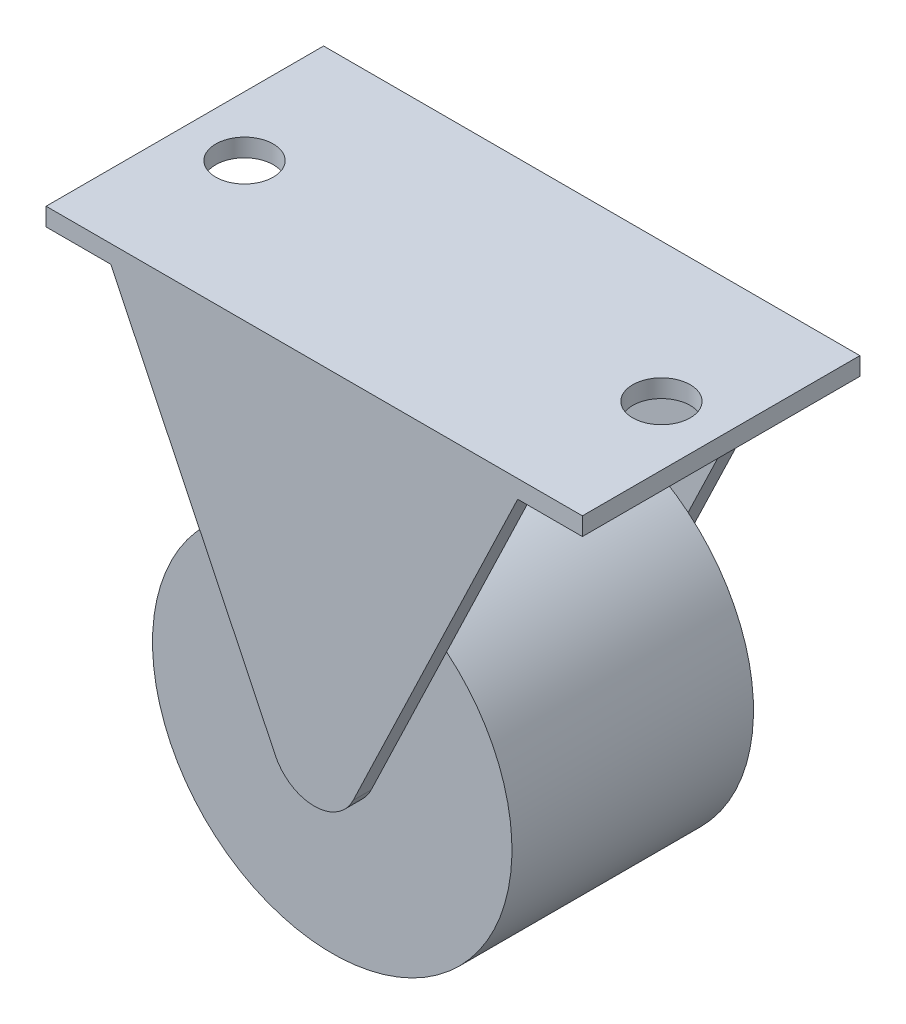
SolidWorks part; units mm, degrees
ref_plane "Front Plane" through (0, 0, 0) normal (0, 0, 1) x (1, 0, 0)
ref_plane "Top Plane" through (0, 0, 0) normal (0, 1, 0) x (1, 0, 0)
ref_plane "Right Plane" through (0, 0, 0) normal (1, 0, 0) x (0, 0, -1)
sketch "Sketch1" plane through (0, 0, 0) normal (0, 1, 0) x (1, 0, 0)
  line L0 (0, 0) -> (0, 9.65) construction
  line L1 (-18.65, 9.65) -> (18.65, 9.65)
  line L2 (-18.65, 9.65) -> (-18.65, -9.65)
  line L3 (-18.65, -9.65) -> (18.65, -9.65)
  line L4 (18.65, 9.65) -> (18.65, -9.65)
  line L5 (-12.5, 0) -> (12.5, 0) construction
  circle A0 centre (-14.5, 0) radius 2
  circle A1 centre (14.5, 0) radius 2
  point P4 (0, 9.65)
  point P6 (-18.65, 0)
  point P15 (-14.437, 0)
  dimension "D3" = 4
  dimension "D4" = 25
  dimension "D1" = 37.3
  dimension "D2" = 19.3
extrude "Boss-Extrude1" add sketch "Sketch1" along normal blind 1.25
sketch "Sketch2" plane through (0, 0, 9.65) normal (0, 0, 1) x (1, 0, 0)
  line L0 (-14.15, 0) -> (14.15, 0)
  line L1 (-18.65, 0) -> (18.65, 0) construction
  line L2 (14.15, 0) -> (2.7049, -23.8608)
  line L3 (-2.7049, -23.8608) -> (-14.15, 0)
  arc A0 (2.7049, -23.8608) -> (-2.7049, -23.8608) centre (0, -22.5633) cw
  point P4 (0, 0)
  point P6 (0, -29.5)
  point P8 (15.3258, 0)
  point P12 (0, -29.5)
  dimension "D3" = 3
  dimension "D1" = 29.5
  dimension "D2" = 4.5
extrude "Boss-Extrude2" add sketch "Sketch2" against normal blind 1.25
extrude "Boss-Extrude3" add sketch "Sketch2<2>" along normal blind 1.25 from surface starting at face at (0, 0.625, -9.65)
sketch "Sketch2<2>" plane through (0, 0, 9.65) normal (0, 0, 1) x (1, 0, 0) same geometry as "Sketch2"
sketch "Sketch3" plane through (0, 0, 8.4) normal (0, 0, -1) x (-1, 0, 0)
  circle A0 centre (0, -22.5633) radius 12.5
  arc A1 (-2.7049, -23.8608) -> (2.7049, -23.8608) centre (0, -22.5633) ccw construction
  dimension "D1" = 25
extrude "Boss-Extrude4" add sketch "Sketch3" along normal up to surface (16.8 mm away) up to face at (0, -12.356, -8.4)
